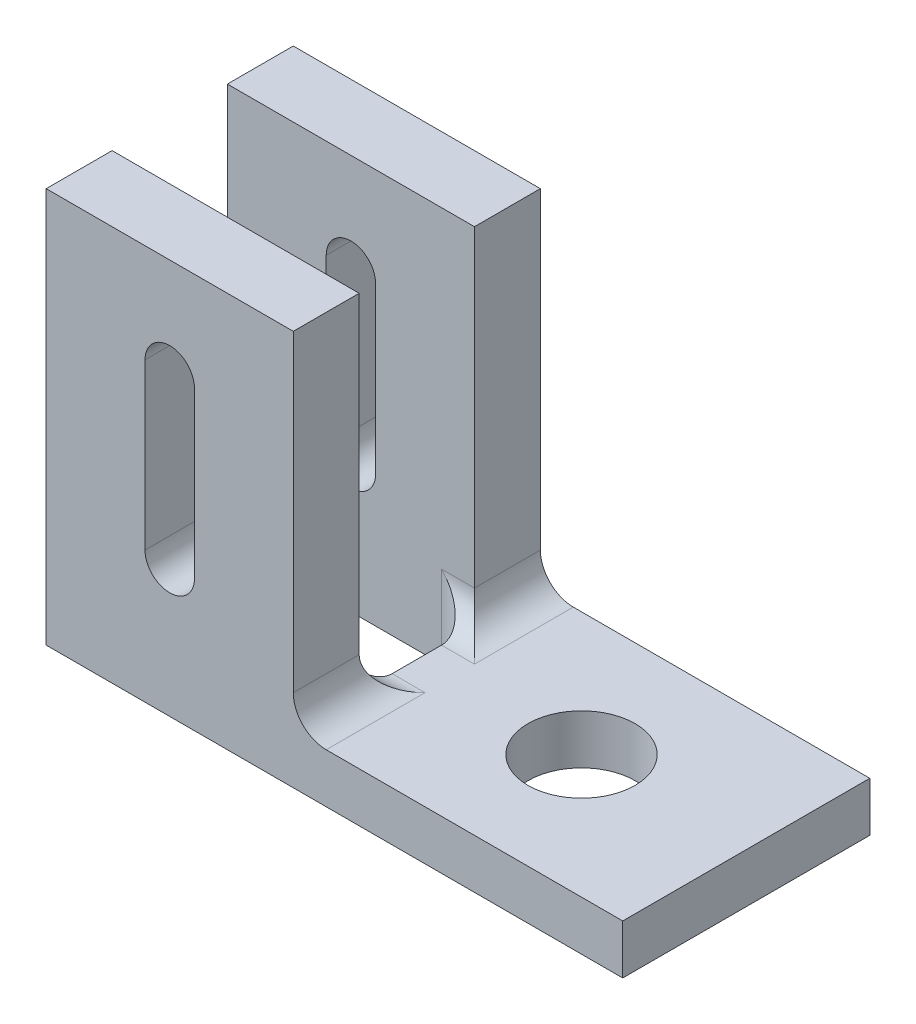
SolidWorks part; units mm, degrees
ref_plane "前视基准面" through (0, 0, 0) normal (0, 0, 1) x (1, 0, 0)
ref_plane "上视基准面" through (0, 0, 0) normal (0, 1, 0) x (1, 0, 0)
ref_plane "右视基准面" through (0, 0, 0) normal (1, 0, 0) x (0, 0, -1)
sketch "草图1" plane through (0, 0, 0) normal (0, 0, 1) x (1, 0, 0)
  line L0 (-3.258, 3.8389) -> (16.742, 3.8389)
  line L1 (-18.258, 24.8389) -> (-3.258, 24.8389)
  line L2 (-18.258, 24.8389) -> (-18.258, 0.8389)
  line L4 (-3.258, 24.8389) -> (-3.258, 3.8389)
  line L5 (16.742, 3.8389) -> (16.742, 0.8389)
  line L6 (-18.258, 0.8389) -> (16.742, 0.8389)
  line L7 (-12.258, 18.8389) -> (-12.258, 8.8389)
  line L9 (-9.258, 8.8389) -> (-9.258, 18.8389)
  line L11 (-10.758, 32.4) -> (-10.758, -13.5814) construction
  arc A0 (-9.258, 18.8389) -> (-12.258, 18.8389) centre (-10.758, 18.8389) ccw
  arc A1 (-12.258, 8.8389) -> (-9.258, 8.8389) centre (-10.758, 8.8389) ccw
  dimension "D1" = 3
  dimension "D2" = 20
  dimension "D3" = 24
  dimension "D4" = 15
  dimension "D5" = 3
  dimension "D6" = 10
  dimension "D7" = 6
  dimension "D8" = 7.5
extrude "凸台-拉伸1" add sketch "草图1" along normal blind 15
sketch "草图2" plane through (0, 24.8389, 0) normal (0, 1, 0) x (1, 0, 0)
  line L0 (-18.258, -4) -> (-18.258, -11)
  line L1 (-18.258, -15) -> (-18.258, 0) construction
  line L2 (-18.258, -11) -> (-8.258, -11)
  line L3 (-8.258, -11) -> (-8.258, -4)
  line L4 (-8.258, -4) -> (-18.258, -4)
  line L5 (-3.258, -15) -> (-3.258, 0) construction
  line L6 (-27.8001, -7.5) -> (19.1089, -7.5) construction
  line L7 (16.742, 0) -> (-3.258, 0) construction
  line L8 (16.742, -15) -> (-3.258, -15) construction
  circle A0 centre (6.742, -7.5) radius 3.25
  dimension "D3" = 6.5
  dimension "D4" = 10
  dimension "D1" = 10
  dimension "D2" = 7
extrude "切除-拉伸1" cut sketch "草图2" against normal blind 37
sketch "草图3" plane through (-3.258, 0, 0) normal (1, 0, 0) x (0, 0, -1)
  line L0 (-7.5, 25.8969) -> (-7.5, -7.0989) construction
  line L1 (-15, 3.8389) -> (-15, 24.8389) construction
  line L2 (0, 3.8389) -> (0, 24.8389) construction
  line L3 (-15, 24.8389) -> (0, 24.8389) construction
  line L4 (-11, 24.8389) -> (-4, 24.8389)
  line L5 (-11, 24.8389) -> (-11, -0.1611)
  line L6 (-11, -0.1611) -> (-4, -0.1611)
  line L7 (-4, 24.8389) -> (-4, -0.1611)
  dimension "D1" = 7
  dimension "D2" = 25
extrude "切除-拉伸2" cut sketch "草图3" against normal blind 37
fillet "圆角1" radius 2 2 edges at (-3.258, 2.3389, 4) (-3.258, 2.3389, 11)
fillet "圆角2" radius 2 4 edges at (-3.258, 3.8389, 2) (-3.258, 3.8389, 13) (-4.258, 3.8389, 11) (-4.258, 3.8389, 4)
